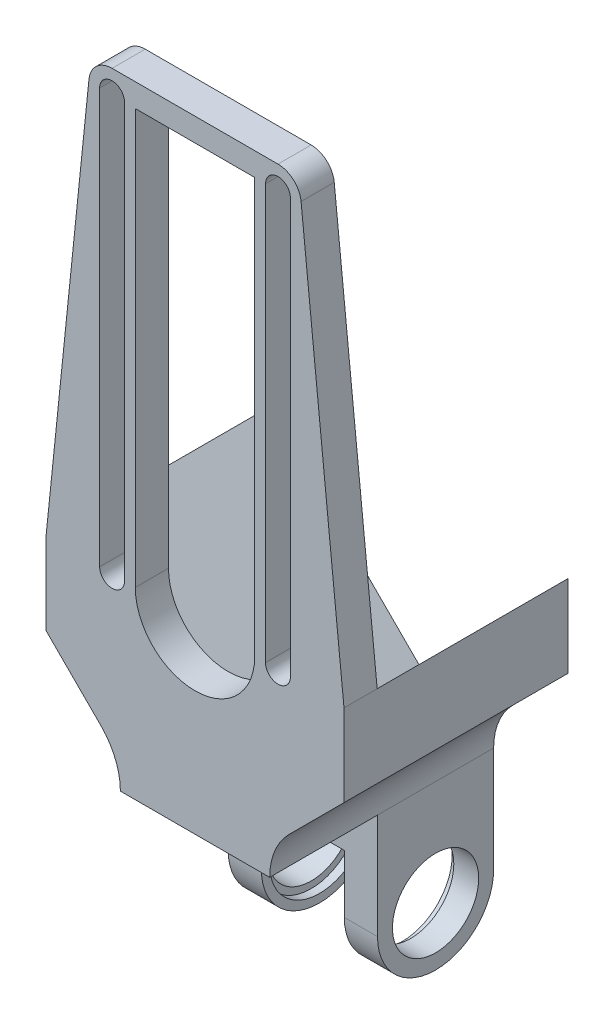
SolidWorks part; units mm, degrees
ref_plane "Alzado" through (0, 0, 0) normal (0, 0, 1) x (1, 0, 0)
ref_plane "Planta" through (0, 0, 0) normal (0, 1, 0) x (1, 0, 0)
ref_plane "Vista lateral" through (0, 0, 0) normal (1, 0, 0) x (0, 0, -1)
sketch "Croquis1" plane through (0, 0, 0) normal (1, 0, 0) x (0, 0, -1)
  line L0 (-7, 0) -> (-7, 7)
  line L1 (-7, 7) -> (7, 7)
  line L2 (7, 7) -> (7, 0)
  circle A0 centre (0, 0) radius 5.2
  circle A1 centre (0, 0) radius 6
  circle A2 centre (0, 0) radius 7
  dimension "D1" = 10.4
  dimension "D2" = 12
  dimension "D3" = 14
extrude "Saliente-Extruir1" add sketch "Croquis1" against normal blind 3 from offset 9 contours A1 A0 region at (0, 0, 5.8303)
extrude "Saliente-Extruir2" add sketch "Croquis1<3>" against normal blind 4 from offset 9 contours A2 L1 L0 | A2 L2 L1 | A2 A1 region at (0, 4.8097, 4.8097) region at (0, 5.4364, 5.4364) region at (0, 5.4364, -5.4364)
sketch "Croquis1<3>" plane through (0, 0, 0) normal (1, 0, 0) x (0, 0, -1) same geometry as "Croquis1"
extrude "Saliente-Extruir3" add sketch "Croquis1<4>" along normal blind 4 from offset 9 separate body contours A2 L1 L0 | A2 L2 L1 | A2 A1 region at (0, 4.8097, 4.8097) region at (0, 5.4364, 5.4364) region at (0, 5.4364, -5.4364) offset against normal yes
sketch "Croquis1<4>" plane through (0, 0, 0) normal (1, 0, 0) x (0, 0, -1) same geometry as "Croquis1"
extrude "Saliente-Extruir4" add sketch "Croquis1<5>" along normal blind 3 from offset 9 contours A1 A0 region at (0, 0, 5.8303) offset against normal yes
sketch "Croquis1<5>" plane through (0, 0, 0) normal (1, 0, 0) x (0, 0, -1) same geometry as "Croquis1"
sketch "Croquis2" plane through (0, 0, 0) normal (0, 0, 1) x (1, 0, 0)
  line L0 (-5, 7) -> (0, 7) construction
  line L1 (0, 7) -> (0, 0) construction
  line L2 (0, 7) -> (0, 16.8995)
  line L3 (0, 16.8995) -> (17.9605, 34.86)
  line L4 (17.9605, 34.86) -> (22.9103, 29.9103)
  line L5 (22.9103, 29.9103) -> (0, 7)
  line L6 (0, 7) -> (5, 7) construction
  line L7 (5, 0) -> (5, 7) construction
  line L8 (8.9803, 25.8798) -> (13.93, 20.93) construction
  line L9 (9, 7) -> (9, 16)
  line L10 (-9, 7) -> (9, 7)
  line L11 (0, 16.8995) -> (-17.9605, 34.86)
  line L12 (-17.9605, 34.86) -> (-22.9103, 29.9103)
  line L13 (-22.9103, 29.9103) -> (0, 7)
  line L14 (-9, 7) -> (-9, 16)
  line L15 (-17.9605, 34.86) -> (-17.9605, 24.9605)
  line L16 (17.9605, 34.86) -> (17.9605, 24.9605)
  dimension "D1" = 45
  dimension "D2" = 7
  dimension "D3" = 25.4
extrude "Saliente-Extruir5" add sketch "Croquis2" along normal blind 7 and the other way blind 7 contours L12 L13 L2 L11 | L5 L4 L3 L2 | L5 L10 L9 | L14 L10 L13 region at (-8.9803, 20.93, 0) region at (8.9803, 20.93, 0) region at (6, 10, 0) region at (-6, 10, 0)
ref_plane "Plano1" through (8.4497, 8.4497, 0) normal (0.7071, 0.7071, 0) x (0.7071, -0.7071, 0)
sketch "Croquis3" plane through (8.4497, 8.4497, 0) normal (0.7071, 0.7071, 0) x (0.7071, -0.7071, 0)
  line L0 (-24.6497, 7) -> (-24.6497, -7) construction
  line L2 (-11.9497, 7) -> (-37.3497, 7) construction
  line L3 (-11.9497, -7) -> (-37.3497, -7) construction
  circle A1 centre (-24.6497, 0) radius 1.7
  dimension "D1" = 3.4
extrude "Cortar-Extruir1" cut sketch "Croquis3" against normal up to surface (7 mm away) up to face at (-13.4803, 20.4803, 0)
ref_plane "Plano2" through (-8.4497, 8.4497, 0) normal (-0.7071, 0.7071, 0) x (0.7071, 0.7071, 0)
sketch "Croquis4" plane through (-8.4497, 8.4497, 0) normal (-0.7071, 0.7071, 0) x (0.7071, 0.7071, 0)
  line L0 (24.6497, 7) -> (24.6497, -7) construction
  line L1 (11.9497, 7) -> (37.3497, 7) construction
  line L2 (11.9497, -7) -> (37.3497, -7) construction
  circle A0 centre (24.6497, 0) radius 1.7
  dimension "D1" = 3.4
extrude "Cortar-Extruir2" cut sketch "Croquis4" against normal up to surface (7 mm away) up to face at (13.4803, 20.4803, 0)
ref_plane "Plano3" through (-3.5, 3.5, 0) normal (0.7071, -0.7071, 0) x (-0.7071, -0.7071, 0)
sketch "Croquis5" plane through (-3.5, 3.5, 0) normal (0.7071, -0.7071, 0) x (-0.7071, -0.7071, 0)
  circle A0 centre (-24.6497, 0) radius 3.2
  dimension "D1" = 6.4
extrude "Cortar-Extruir3" cut sketch "Croquis5" against normal blind 3.4
ref_plane "Plano4" through (3.5, 3.5, 0) normal (-0.7071, -0.7071, 0) x (-0.7071, 0.7071, 0)
sketch "Croquis6" plane through (3.5, 3.5, 0) normal (-0.7071, -0.7071, 0) x (-0.7071, 0.7071, 0)
  circle A0 centre (24.6497, 0) radius 3.2
  dimension "D1" = 6.4
extrude "Cortar-Extruir4" cut sketch "Croquis6" against normal blind 3.4
fillet "Redondeo1" radius 8 2 edges at (9, 16, 0) (-9, 16, 0)
ref_plane "Plano5" through (0, 0, 7) normal (0, 0, 1) x (1, 0, 0)
sketch "Croquis7" plane through (0, 0, 7) normal (0, 0, 1) x (1, 0, 0)
  line L0 (0, 16.8995) -> (17.9605, 34.86)
  line L1 (17.9605, 34.86) -> (17.9605, 24.9605)
  line L2 (17.9605, 24.9605) -> (11.3431, 18.3431)
  line L3 (9, 12.6863) -> (-9, 12.6863)
  line L4 (-11.3431, 18.3431) -> (-17.9605, 24.9605)
  line L5 (-17.9605, 24.9605) -> (-17.9605, 34.86)
  line L6 (-17.9605, 34.86) -> (0, 16.8995)
  line L7 (0, 34.86) -> (17.9605, 34.86) construction
  line L8 (10, 34.86) -> (10, 84.86) construction
  line L9 (8.5, 84.86) -> (8.5, 34.86)
  line L10 (11.5, 84.86) -> (11.5, 34.86)
  line L11 (7.2, 84.86) -> (7.2, 34.86)
  line L12 (12.8, 84.86) -> (12.8, 34.86)
  line L13 (17.9605, 34.86) -> (12.7853, 85.1467)
  line L14 (0, 34.86) -> (0, 84.86) construction
  line L15 (-7.2, 84.86) -> (7.2, 84.86)
  line L16 (0, 84.86) -> (0, 87.66)
  line L17 (-10, 87.66) -> (10, 87.66)
  line L18 (-17.9605, 34.86) -> (-12.7853, 85.1467)
  line L19 (-12.8, 84.86) -> (-12.8, 34.86)
  line L20 (-11.5, 84.86) -> (-11.5, 34.86)
  line L21 (-8.5, 84.86) -> (-8.5, 34.86)
  line L22 (-7.2, 84.86) -> (-7.2, 34.86)
  arc A0 (11.3431, 18.3431) -> (9, 12.6863) centre (17, 12.6863) ccw
  arc A1 (11.3431, 18.3431) -> (9, 12.6863) centre (17, 12.6863) ccw construction
  arc A2 (-9, 12.6863) -> (-11.3431, 18.3431) centre (-17, 12.6863) ccw
  arc A3 (8.5, 34.86) -> (11.5, 34.86) centre (10, 34.86) ccw
  arc A4 (11.5, 84.86) -> (8.5, 84.86) centre (10, 84.86) ccw
  arc A5 (7.2, 34.86) -> (12.8, 34.86) centre (10, 34.86) ccw
  arc A6 (12.8, 84.86) -> (7.2, 84.86) centre (10, 84.86) ccw
  arc A7 (7.2, 34.86) -> (-7.2, 34.86) centre (0, 34.86) cw
  arc A8 (-7.2, 34.86) -> (-12.8, 34.86) centre (-10, 34.86) cw
  arc A9 (-8.5, 34.86) -> (-11.5, 34.86) centre (-10, 34.86) cw
  arc A10 (-11.5, 84.86) -> (-8.5, 84.86) centre (-10, 84.86) cw
  arc A11 (-12.8, 84.86) -> (-7.2, 84.86) centre (-10, 84.86) cw
  dimension "D1" = 3
extrude "Saliente-Extruir6" add sketch "Croquis7" along normal blind 4 from offset 9 separate body contours L19 A11 L18 L6 L0 L13 A6 L12 A5 A7 A8 | A11 L19 A8 L22 L20 A10 L21 A9 | L12 A6 L11 A5 A4 L10 A3 L9 | L17 A11 L15 L16 | A6 L17 L16 L15 region at (-8.4349, 26.4251, 7) region at (12.2382, 84.9749, 7) region at (-11.5014, 86.5239, 7) region at (3.9255, 86.3197, 7) region at (-3.9255, 86.3197, 7)
extrude "Saliente-Extruir7" add sketch "Croquis7<4>" along normal blind 13 contours A2 L3 A0 L2 L1 L0 L6 L5 L4 region at (9.2788, 25.5813, 7)
sketch "Croquis7<4>" plane through (0, 0, 7) normal (0, 0, 1) x (1, 0, 0) same geometry as "Croquis7"
